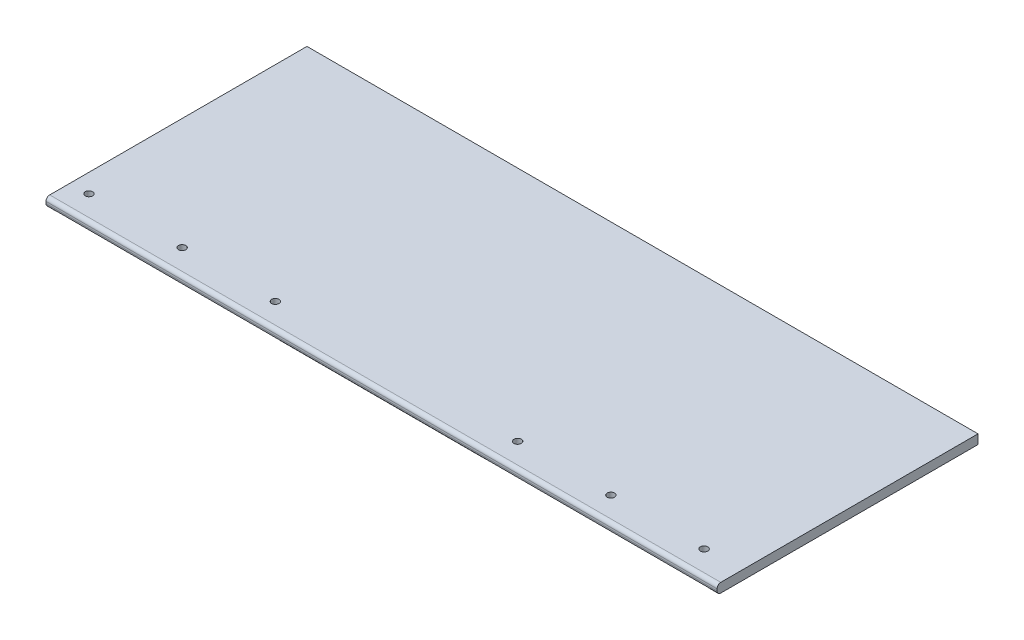
SolidWorks part; units mm, degrees
material "6061 Alloy"
ref_plane "Front Plane" through (0, 0, 0) normal (0, 0, 1) x (1, 0, 0)
ref_plane "Top Plane" through (0, 0, 0) normal (0, 1, 0) x (1, 0, 0)
ref_plane "Right Plane" through (0, 0, 0) normal (1, 0, 0) x (0, 0, -1)
sketch "Sketch1" plane through (0, 0, 0) normal (0, 1, 0) x (1, 0, 0)
  line L1 (-228.6, 88.9) -> (228.6, 88.9)
  line L2 (-228.6, 88.9) -> (-228.6, -88.9)
  line L3 (-228.6, -88.9) -> (228.6, -88.9)
  line L4 (228.6, 88.9) -> (228.6, -88.9)
  line L5 (-228.6, 88.9) -> (228.6, -88.9) construction
  line L6 (-228.6, -88.9) -> (228.6, 88.9) construction
  circle A10 centre (203.2, -72.3392) radius 2.5019 construction
  circle A11 centre (139.7, -72.3392) radius 2.5019 construction
  circle A12 centre (76.2, -72.3392) radius 2.5019 construction
  circle A13 centre (-88.9, -72.3392) radius 2.5019 construction
  circle A14 centre (-152.4, -72.3392) radius 2.5019 construction
  circle A15 centre (-215.9, -72.3392) radius 2.5019 construction
  circle A16 centre (203.2, -72.3392) radius 2.5019
  circle A17 centre (139.7, -72.3392) radius 2.5019
  circle A18 centre (76.2, -72.3392) radius 2.5019
  circle A19 centre (-88.9, -72.3392) radius 2.5019
  circle A20 centre (-152.4, -72.3392) radius 2.5019
  circle A21 centre (-215.9, -72.3392) radius 2.5019
  point P0 (0, 0)
  dimension "D1" = 177.8
  dimension "D2" = 457.2
extrude "Boss-Extrude1" add sketch "Sketch1" along normal blind 6.35
sketch "Sketch2" plane through (-228.6, 0, 0) normal (-1, 0, 0) x (0, 0, 1)
  line L0 (-88.9, 6.35) -> (88.9, 6.35) construction
  line L1 (88.9, 6.35) -> (88.9, 0) construction
  circle A0 centre (85.725, 3.175) radius 1.5875
  dimension "D1" = 3.175
  dimension "D2" = 3.175
  dimension "D3" = 3.175
extrude "Cut-Extrude1" [suppressed] cut sketch "Sketch2" against normal through all
fillet "Fillet1" radius 2.54 2 edges at (0, 0, 88.9) (0, 6.35, 88.9)
sketch "Sketch3" plane through (228.6, 0, 0) normal (1, 0, 0) x (0, 0, -1)
  line L0 (88.9, 6.35) -> (88.9, 0) construction
  line L1 (-48.26, 4.572) -> (-33.02, 4.572)
  line L2 (-48.26, 4.572) -> (-48.26, 1.27)
  line L3 (-48.26, 1.27) -> (-33.02, 1.27)
  line L4 (-33.02, 4.572) -> (-33.02, 1.27)
  line L5 (-48.26, 4.572) -> (-33.02, 1.27) construction
  line L6 (-48.26, 1.27) -> (-33.02, 4.572) construction
  line L7 (-86.36, 0) -> (88.9, 0) construction
  point P0 (-40.64, 2.921)
  dimension "D1" = 15.24
  dimension "D2" = 129.54
  dimension "D3" = 3.302
  dimension "D4" = 1.27
sketch "Sketch4" plane through (0, 0, 0) normal (0, -1, 0) x (1, 0, 0)
  line L0 (228.6, 86.36) -> (228.6, -88.9) construction
  line L2 (-228.6, 88.9) -> (228.6, 88.9) construction
  circle A1 centre (203.2, 72.3392) radius 2.54
  dimension "D2" = 5.08
  dimension "D1" = 16.5608
  dimension "D3" = 25.4
extrude "Cut-Extrude3" cut sketch "Sketch4" against normal through all
sketch "Sketch5" plane through (0, 0, 0) normal (0, -1, 0) x (1, 0, 0)
  line L0 (-228.6, 88.9) -> (228.6, 88.9) construction
  line L1 (-222.25, 61.1632) -> (-69.85, 61.1632)
  line L2 (-222.25, 61.1632) -> (-222.25, 88.9)
  line L3 (-222.25, 88.9) -> (-69.85, 88.9)
  line L4 (-69.85, 61.1632) -> (-69.85, 88.9)
  line L5 (-228.6, -88.9) -> (-228.6, 86.36) construction
  dimension "D1" = 6.35
  dimension "D2" = 152.4
  dimension "D3" = 27.7368
extrude "Cut-Extrude4" cut sketch "Sketch5" against normal blind 1.2192
ref_axis "Axis1" through (0, 0, -88.9) along (0, 0.0143, 0.9999)
ref_plane "Plane1" through (0, 0, 0) normal (1, 0, 0) x (0, 0, -1)
mirror "Mirror1" about plane through (0, 0, 0) normal (1, 0, 0) of "Cut-Extrude4"
